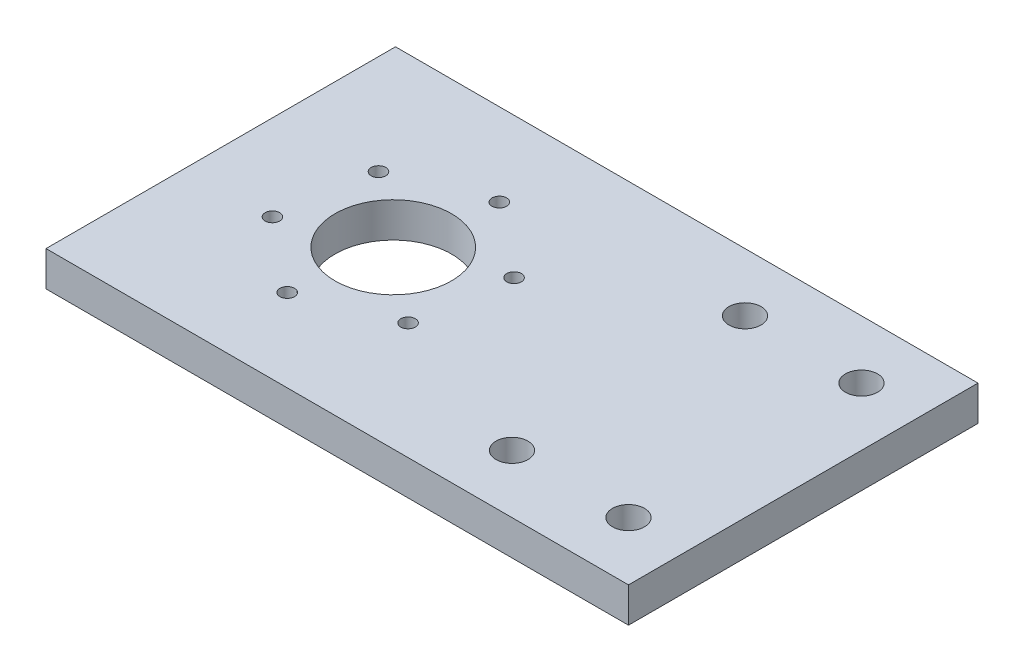
SolidWorks part; units mm, degrees
ref_plane "Front Plane" through (0, 0, 0) normal (0, 0, 1) x (1, 0, 0)
ref_plane "Top Plane" through (0, 0, 0) normal (0, 1, 0) x (1, 0, 0)
ref_plane "Right Plane" through (0, 0, 0) normal (1, 0, 0) x (0, 0, -1)
sketch "Sketch1" plane through (0, 0, 0) normal (0, 1, 0) x (1, 0, 0)
  line L1 (0, 0) -> (100, 0)
  line L2 (0, 0) -> (0, 60)
  line L3 (0, 60) -> (100, 60)
  line L4 (100, 0) -> (100, 60)
  dimension "D1" = 100
  dimension "D2" = 60
extrude "Boss-Extrude1" add sketch "Sketch1" along normal blind 6
sketch "Sketch2" plane through (0, 6, 0) normal (0, 1, 0) x (1, 0, 0)
  line L1 (100, 0) -> (100, 60) construction
  line L7 (100, 30) -> (0, 30) construction
  line L8 (0, 60) -> (0, 0) construction
  circle A0 centre (29.6153, 30) radius 10
  circle A5 centre (70, 50) radius 2.75
  circle A6 centre (90, 50) radius 2.75
  circle A7 centre (70, 10) radius 2.75
  circle A8 centre (90, 10) radius 2.75
  point P7 (100, 30)
  dimension "D1" = 20
extrude "Cut-Extrude1" cut sketch "Sketch2" against normal blind 6
sketch "Sketch3" plane through (0, 6, 0) normal (0, 1, 0) x (1, 0, 0)
  circle A0 centre (31.9984, 45.8215) radius 1.25 construction
  circle A1 centre (31.9984, 45.8215) radius 1.25
  circle A2 centre (17.105, 39.9745) radius 1.25 construction
  circle A3 centre (17.105, 39.9745) radius 1.25
  circle A4 centre (44.5087, 35.847) radius 1.25 construction
  circle A5 centre (14.722, 24.153) radius 1.25 construction
  circle A6 centre (27.2323, 14.1785) radius 1.25 construction
  circle A7 centre (42.1257, 20.0255) radius 1.25 construction
  circle A8 centre (31.9984, 45.8215) radius 1.25
  circle A9 centre (44.5087, 35.847) radius 1.25
  circle A10 centre (17.105, 39.9745) radius 1.25
  circle A11 centre (14.722, 24.153) radius 1.25
  circle A12 centre (27.2323, 14.1785) radius 1.25
  circle A13 centre (42.1257, 20.0255) radius 1.25
  point P20 (0, 0)
extrude "Cut-Extrude2" cut sketch "Sketch3" against normal through all contours A1 | A9 | A13 | A12 | A11 | A3 region at (31.9984, 6, -45.8215) region at (44.5087, 6, -35.847) region at (14.722, 6, -24.153) region at (27.2323, 6, -14.1785) region at (42.1257, 6, -20.0255)
